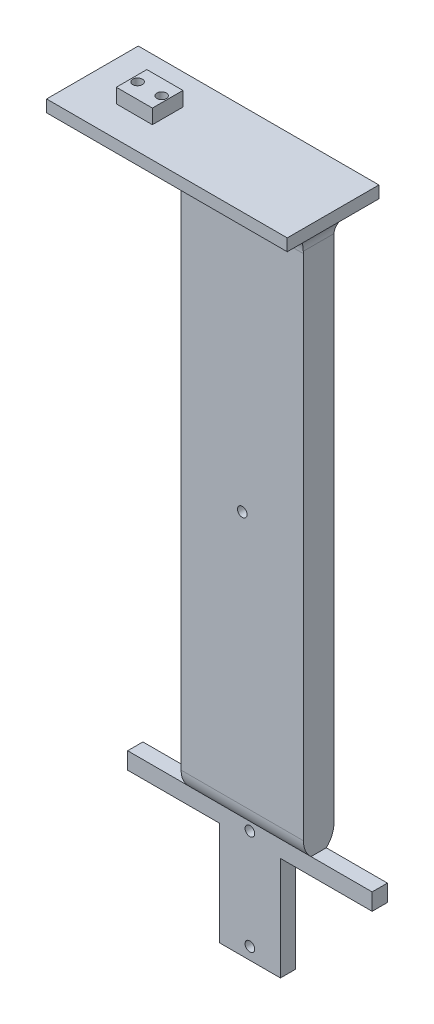
SolidWorks part; units mm, degrees
ref_plane "Front Plane" through (0, 0, 0) normal (0, 0, 1) x (1, 0, 0)
ref_plane "Top Plane" through (0, 0, 0) normal (0, 1, 0) x (1, 0, 0)
ref_plane "Right Plane" through (0, 0, 0) normal (1, 0, 0) x (0, 0, -1)
sketch "Sketch1" plane through (0, 0, 0) normal (0, 1, 0) x (1, 0, 0)
  line L1 (-50, 19.05) -> (50, 19.05)
  line L2 (-50, 19.05) -> (-50, -19.05)
  line L3 (-50, -19.05) -> (50, -19.05)
  line L4 (50, 19.05) -> (50, -19.05)
  line L5 (-50, 19.05) -> (50, -19.05) construction
  line L6 (-50, -19.05) -> (50, 19.05) construction
  point P0 (0, 0)
  dimension "D1" = 100
  dimension "D2" = 38.1
extrude "Boss-Extrude1" add sketch "Sketch1" along normal blind 5
sketch "Sketch2" plane through (0, 5, 0) normal (0, 1, 0) x (1, 0, 0)
  line L1 (-33.7366, 6.35) -> (-18.7366, 6.35)
  line L2 (-33.7366, 6.35) -> (-33.7366, -6.35)
  line L3 (-33.7366, -6.35) -> (-18.7366, -6.35)
  line L4 (-18.7366, 6.35) -> (-18.7366, -6.35)
  line L5 (-33.7366, 6.35) -> (-18.7366, -6.35) construction
  line L6 (-33.7366, -6.35) -> (-18.7366, 6.35) construction
  point P0 (-26.2366, 0)
  dimension "D1" = 12.7
  dimension "D2" = 15
extrude "Boss-Extrude2" add sketch "Sketch2" along normal blind 6
sketch "Sketch3" plane through (0, 11, 0) normal (0, 1, 0) x (1, 0, 0)
  line L0 (-33.7366, 6.35) -> (-33.7366, -6.35) construction
  circle A0 centre (-21.2366, 0) radius 2
  circle A1 centre (-31.2366, 0) radius 2
  dimension "D1" = 4
  dimension "D2" = 4
  dimension "D3" = 10
  dimension "D4" = 2.5
sketch "Sketch11" plane through (0, 11, 0) normal (0, 1, 0) x (1, 0, 0)
  point P0 (-31.2366, 0)
  point P3 (-21.2366, 0)
hole_wizard "Tap Drill for M4x0.7 Tap1" positions "Sketch11" profile "Sketch10" hole size "M4x0.7" standard "ANSI Metric" end condition through all
sketch "Sketch10" plane through (-31.2366, 11, 0) normal (1, 0, 0) x (0, 0, 1)
  line L0 (0, 0) -> (0, 11)
  line L1 (0, 11) -> (1.65, 11)
  line L2 (1.65, 11) -> (1.65, 0)
  line L5 (1.65, 0) -> (0, 0)
  line L11 (0, -6.35) -> (0, 107.95) construction
  dimension "Thru Hole Dia." = 3.3
  dimension "Thru Hole Depth" = 11
extrude "Cut-Extrude1" cut sketch "Sketch3" against normal through all
sketch "Sketch12" plane through (0, 0, 0) normal (0, -1, 0) x (1, 0, 0)
  circle A0 centre (-31.2366, 0) radius 3.5
  circle A1 centre (-21.2366, 0) radius 3.5
  dimension "D1" = 7
  dimension "D2" = 7
extrude "Cut-Extrude2" cut sketch "Sketch12" against normal blind 3
sketch "Sketch13" plane through (0, 0, 0) normal (0, -1, 0) x (1, 0, 0)
  line L0 (50, 19.05) -> (50, -19.05) construction
  line L1 (-6.8, 6.35) -> (44, 6.35)
  line L2 (-6.8, 6.35) -> (-6.8, -6.35)
  line L3 (-6.8, -6.35) -> (44, -6.35)
  line L4 (44, 6.35) -> (44, -6.35)
  line L5 (-6.8, 6.35) -> (44, -6.35) construction
  line L6 (-6.8, -6.35) -> (44, 6.35) construction
  point P0 (18.6, 0)
  point P7 (50, 0)
  dimension "D1" = 50.8
  dimension "D2" = 12.7
  dimension "D3" = 6
extrude "Boss-Extrude3" add sketch "Sketch13" along normal blind 228.6
sketch "Sketch14" plane through (0, -228.6, 0) normal (0, -1, 0) x (1, 0, 0)
  line L0 (18.6, 6.35) -> (18.6, -6.35) construction
  line L1 (44, 6.35) -> (-6.8, 6.35) construction
  line L2 (-6.8, -6.35) -> (44, -6.35) construction
  line L3 (-6.8, 0) -> (44, 0) construction
  line L4 (-6.8, 6.35) -> (-6.8, -6.35) construction
  line L5 (44, -6.35) -> (44, 6.35) construction
  line L7 (-32.2, 3.175) -> (69.4, 3.175)
  line L8 (-32.2, 3.175) -> (-32.2, -3.175)
  line L9 (-32.2, -3.175) -> (69.4, -3.175)
  line L10 (69.4, 3.175) -> (69.4, -3.175)
  line L11 (-32.2, 3.175) -> (69.4, -3.175) construction
  line L12 (-32.2, -3.175) -> (69.4, 3.175) construction
  point P12 (18.6, 0)
  dimension "D1" = 101.6
  dimension "D2" = 6.35
extrude "Boss-Extrude4" add sketch "Sketch14" along normal blind 7
fillet "Fillet1" radius 10 1 edges at (18.6, -228.6, -6.35)
fillet "Fillet2" radius 10 1 edges at (18.6, -228.6, 6.35)
fillet "Fillet3" radius 10 4 edges at (44, 0, 0) (18.6, 0, -6.35) (-6.8, 0, 0) (18.6, 0, 6.35)
sketch "Sketch15" plane through (0, 0, -3.175) normal (0, 0, -1) x (-1, 0, 0)
  line L0 (-18.6, -228.6) -> (-18.6, -235.6) construction
  line L1 (6.8, -228.6) -> (-44, -228.6) construction
  line L2 (32.2, -235.6) -> (-69.4, -235.6) construction
  line L3 (-69.4, -232.1) -> (32.2, -232.1) construction
  line L4 (-69.4, -235.6) -> (-69.4, -228.6) construction
  line L5 (32.2, -235.6) -> (32.2, -228.6) construction
  circle A0 centre (-18.6, -232.1) radius 2
  dimension "D1" = 4
extrude "Cut-Extrude3" cut sketch "Sketch15" against normal through all
sketch "Sketch16" plane through (0, -235.6, 0) normal (0, -1, 0) x (1, 0, 0)
  line L0 (18.6, 3.175) -> (18.6, -3.175) construction
  line L1 (44, 3.175) -> (-6.8, 3.175) construction
  line L2 (-6.8, -3.175) -> (44, -3.175) construction
  line L3 (-32.2, 0) -> (69.4, 0) construction
  line L4 (-32.2, 3.175) -> (-32.2, -3.175) construction
  line L5 (69.4, -3.175) -> (69.4, 3.175) construction
  line L6 (-32.2, -3.175) -> (69.4, -3.175) construction
  line L7 (5.9, 3.175) -> (31.3, 3.175)
  line L8 (5.9, 3.175) -> (5.9, -3.175)
  line L9 (5.9, -3.175) -> (31.3, -3.175)
  line L10 (31.3, 3.175) -> (31.3, -3.175)
  line L11 (5.9, 3.175) -> (31.3, -3.175) construction
  line L12 (5.9, -3.175) -> (31.3, 3.175) construction
  point P12 (18.6, 0)
  dimension "D1" = 25.4
extrude "Boss-Extrude5" add sketch "Sketch16" along normal blind 43.038
sketch "Sketch17" plane through (0, 0, -3.175) normal (0, 0, -1) x (-1, 0, 0)
  line L0 (-18.6, -228.6) -> (-18.6, -278.638) construction
  line L1 (6.8, -228.6) -> (-44, -228.6) construction
  line L2 (-5.9, -278.638) -> (-31.3, -278.638) construction
  line L3 (-31.3, -257.119) -> (-5.9, -257.119) construction
  line L4 (-31.3, -278.638) -> (-31.3, -235.6) construction
  line L5 (-5.9, -278.638) -> (-5.9, -235.6) construction
  circle A0 centre (-18.6, -273.638) radius 2
  dimension "D1" = 4
  dimension "D2" = 5
extrude "Cut-Extrude4" cut sketch "Sketch17" against normal through all
sketch "Sketch18" plane through (0, 0, 6.35) normal (0, 0, 1) x (1, 0, 0)
  line L0 (44, -115.6456) -> (-6.8, -115.6456) construction
  line L1 (44, -221.2911) -> (44, -10) construction
  line L2 (-6.8, -221.2911) -> (-6.8, -10) construction
  circle A0 centre (18.6, -115.6456) radius 2
  dimension "D1" = 4
extrude "Cut-Extrude5" cut sketch "Sketch18" against normal through all
